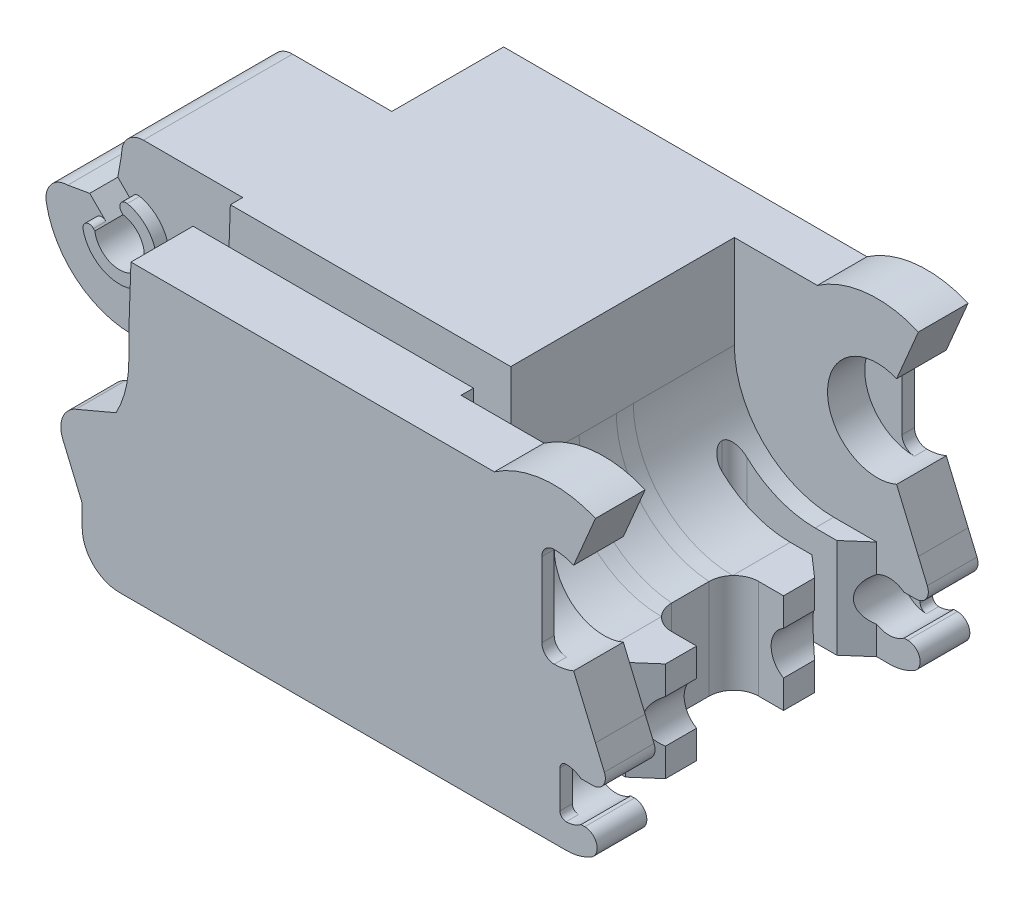
SolidWorks part; units mm, degrees
ref_plane "Front Plane" through (0, 0, 0) normal (0, 0, 1) x (1, 0, 0)
ref_plane "Top Plane" through (0, 0, 0) normal (0, 1, 0) x (1, 0, 0)
ref_plane "Right Plane" through (0, 0, 0) normal (1, 0, 0) x (0, 0, -1)
sketch "Sketch1" plane through (0, 0, 0) normal (0, 0, 1) x (1, 0, 0)
  line L0 (0, 0) -> (8.5, 0) construction
  line L1 (-52.5, 8.5) -> (8.5, 8.5)
  line L2 (-52.5, 8.5) -> (-52.5, -16.5)
  line L3 (-52.5, -16.5) -> (8.5, -16.5)
  line L4 (8.5, 8.5) -> (8.5, -16.5)
  line L5 (0, 0) -> (3.3212, 7.8243) construction
  line L6 (3.3212, 7.8243) -> (1.5629, 3.682)
  line L7 (3.3212, -7.8243) -> (1.5629, -3.682)
  line L8 (2.1605, -10.9) -> (2.1605, -14.1)
  line L9 (2.1605, -10.9) -> (4.6266, -10.9)
  line L10 (2.1605, -14.1) -> (4.6266, -14.1)
  line L11 (-42.7172, 1.9799) -> (-44.9799, -0.2828)
  line L12 (-52.5, -16.5) -> (-34, -16.5)
  line L13 (-52.5, -16.5) -> (-52.5, -6.5)
  line L16 (-42.7172, 1.9799) -> (-44.1314, 3.3941)
  line L17 (-48.1668, 0.8188) -> (-49.6208, 2.2728)
  line L18 (-43, 0) -> (-43.8485, 0.8485) construction
  line L19 (-46.3941, 1.1314) -> (-48.1668, 0.8188)
  line L20 (-43, 7) -> (-4.8218, 7)
  line L21 (-44.9799, -0.2828) -> (-46.3941, 1.1314)
  line L22 (-44.1314, 3.3941) -> (-43.8188, 5.1668)
  line L23 (-43.8188, 5.1668) -> (-45.2728, 6.6208)
  line L24 (-43, -7) -> (-34, -7)
  line L25 (-34, -7) -> (-34, -16.5)
  line L26 (4.6266, -10.9) -> (3.3212, -7.8243)
  line L27 (-34, -7) -> (-34, 0) construction
  line L28 (-38, -7) -> (-38, -16.5)
  line L29 (-43, 0) -> (-45, 0) construction
  circle A0 centre (0, 0) radius 2 construction
  circle A1 centre (-43, 0) radius 2
  circle A2 centre (0, 0) radius 4
  circle A3 centre (0, 0) radius 8.5
  circle A4 centre (0.9605, -12.5) radius 2
  circle A5 centre (0.9605, -12.5) radius 4
  circle A6 centre (-43, 0) radius 7
  circle A8 centre (-43, 0) radius 8.5 construction
  circle A9 centre (-43, 0) radius 9 construction
  point P39 (4.9605, -12.5)
  dimension "D1" = 4
  dimension "D2" = 4
  dimension "D4" = 8
  dimension "D9" = 4
  dimension "D13" = 8
  dimension "D20" = 17
  dimension "D23" = 17
  dimension "D3" = 43
  dimension "D5" = 25
  dimension "D6" = 9.5
  dimension "D8" = 67
  dimension "D10" = 2
  dimension "D12" = 3.2
  dimension "D16" = 3.2
  dimension "D14" = 2
  dimension "D15" = 4.9605
  dimension "D24" = 9
  dimension "D21" = 5
  dimension "D18" = 125
  dimension "D19" = 1.8
  dimension "D25" = 45
  dimension "D7" = 4.5
  dimension "D11" = 2
  dimension "D17" = 5
  dimension "D22" = 0.5
extrude "Boss-Extrude1" add sketch "Sketch1" along normal mid plane 30 contours A6 L23 L22 L16 A1 L21 L19 L17 | L6 A3 L7 A2 | A6 L24 L25 L3 A5 L26 A3 L20 | L9 A5 L10 A4 region at (1.6533, 8.1265, 0) region at (-20.6114, -4.9136, 0) region at (-38.1903, 4.8097, 0) region at (3.3935, -10.7892, 0)
fillet "Fillet1" radius 1 2 edges at (4.6266, -14.1, 0) (4.6266, -10.9, 0)
sketch "Sketch3" plane through (0, 0, 0) normal (0, 0, 1) x (1, 0, 0)
  line L0 (-34, -16.5) -> (0.9605, -16.5) construction
  line L1 (-11.5, 10.2107) -> (7.5521, 10.2107)
  line L2 (-11.5, 10.2107) -> (-11.5, -16.5)
  line L3 (-11.5, -16.5) -> (7.5521, -16.5)
  line L4 (7.5521, 10.2107) -> (7.5521, -16.5)
  dimension "D1" = 11.5
extrude "Cut-Extrude1" cut sketch "Sketch3" against normal offset from surface 4 and the other way offset from surface 4 contours L4 L1 L2 L3 region at (-1.9739, -3.1446, 0) up to face at (-21.008, -3.7662, -15) other way up to face at (-21.008, -3.7662, 15)
sketch "Sketch5" plane through (0, 0, 15) normal (0, 0, 1) x (1, 0, 0)
  line L0 (-43, 7) -> (-4.8218, 7) construction
  line L1 (-34, -7) -> (-73.6432, -7)
  line L2 (-34, -7) -> (-34, 7)
  line L3 (-34, 7) -> (-73.6432, 7)
  line L4 (-73.6432, -7) -> (-73.6432, 7)
extrude "Cut-Extrude2" cut sketch "Sketch5" against normal offset from surface (9 mm away) 5 up to face at (-0.5679, -6.687, 11) offset beyond the face yes
sketch "Sketch6" plane through (0, 0, -15) normal (0, 0, -1) x (-1, 0, 0)
  line L8 (34, -7) -> (73.6432, -7)
  line L9 (73.6432, -7) -> (73.6432, 7)
  line L10 (73.6432, 7) -> (34, 7)
  line L11 (34, 7) -> (34, -7)
  line L12 (34, -7) -> (73.6432, -7)
  line L13 (73.6432, -7) -> (73.6432, 7)
  line L14 (73.6432, 7) -> (34, 7)
  line L15 (34, 7) -> (34, -7)
  line M10 (34, -7) -> (43, -7)
  arc M11 (43, -7) -> (49.6208, 2.2728) centre (43, 0) ccw
  line M12 (49.6208, 2.2728) -> (48.1668, 0.8188)
  line M13 (48.1668, 0.8188) -> (46.3941, 1.1314)
  line M14 (46.3941, 1.1314) -> (44.9799, -0.2828)
  arc M15 (44.9799, -0.2828) -> (42.7172, 1.9799) centre (43, 0) cw
  line M16 (42.7172, 1.9799) -> (44.1314, 3.3941)
  line M17 (44.1314, 3.3941) -> (43.8188, 5.1668)
  line M18 (43.8188, 5.1668) -> (45.2728, 6.6208)
  arc M19 (45.2728, 6.6208) -> (43, 7) centre (43, 0) ccw
  line M20 (43, 7) -> (4.8218, 7)
  dimension "D1" = 0
extrude "Cut-Extrude3" cut sketch "Sketch6" against normal offset from surface (9 mm away) 5 contours M10 M11 M12 M13 M14 M15 M16 M17 M18 M19 M20 region at (-40.4606, -0.4936, -15) up to face at (-0.5679, -6.687, -11) offset beyond the face yes
sketch "Sketch7" plane through (0, 0, 0) normal (0, 0, 1) x (1, 0, 0)
  line L9 (-45.2728, 6.6208) -> (-43.8188, 5.1668)
  line L10 (-45.2728, 6.6208) -> (-43.8188, 5.1668)
  line L11 (-43.8188, 5.1668) -> (-44.1314, 3.3941)
  line L12 (-43.8188, 5.1668) -> (-44.1314, 3.3941)
  line L13 (-44.1314, 3.3941) -> (-42.7172, 1.9799)
  line L14 (-44.1314, 3.3941) -> (-42.7172, 1.9799)
  line L15 (-34, 7) -> (-43, 7)
  line L16 (-34, -7) -> (-34, 7)
  line L17 (-44.9799, -0.2828) -> (-46.3941, 1.1314)
  line L25 (-34, -7) -> (-34, 7)
  line L27 (-44.9799, -0.2828) -> (-46.3941, 1.1314)
  line L28 (-46.3941, 1.1314) -> (-48.1668, 0.8188)
  line L29 (-46.3941, 1.1314) -> (-48.1668, 0.8188)
  line L30 (-48.1668, 0.8188) -> (-49.6208, 2.2728)
  line L31 (-48.1668, 0.8188) -> (-49.6208, 2.2728)
  line L32 (-34, 7) -> (-43, 7)
  line L34 (-43, -7) -> (-34, -7)
  line L37 (-43, -7) -> (-34, -7)
  arc A1 (-43, 7) -> (-45.2728, 6.6208) centre (-43, 0) ccw
  arc A5 (-43, 7) -> (-45.2728, 6.6208) centre (-43, 0) ccw
  arc A9 (-44.9799, -0.2828) -> (-42.7172, 1.9799) centre (-43, 0) ccw
  arc A10 (-44.9799, -0.2828) -> (-42.7172, 1.9799) centre (-43, 0) ccw
  arc A11 (-49.6208, 2.2728) -> (-43, -7) centre (-43, 0) ccw
  arc A12 (-49.6208, 2.2728) -> (-43, -7) centre (-43, 0) ccw
  dimension "D1" = 0
fillet "Fillet2" radius 1.75 2 edges at (-49.6208, 2.2728, 0) (-45.2728, 6.6208, 0)
sketch "Sketch8" [suppressed] plane through (0, 0, -4.25) normal (0, 0, 1) x (1, 0, 0)
  line L0 (-53, 7) -> (-43, 7)
  line L1 (-43, 7) -> (-43, -7)
  line L2 (-43, -7) -> (-53, -7)
  arc A0 (-54.9799, -0.2828) -> (-52.7172, 1.9799) centre (-53, 0) ccw construction
  arc A1 (-54.9799, -0.2828) -> (-52.7172, 1.9799) centre (-53, 0) ccw
  circle A2 centre (-53, 0) radius 6 construction
  circle A3 centre (-53, 0) radius 7
  dimension "D1" = 17
sketch "Sketch10" plane through (0, 0, 6) normal (0, 0, 1) x (1, 0, 0)
  line L0 (-34.25, 0) -> (-34.25, 7)
  line L1 (-38, -7) -> (-38, -16.5) construction
  line L2 (-38, -7) -> (-38, -16.5)
  line L3 (-34, 7) -> (-37.75, 7)
  line L6 (-42.0708, 7) -> (-34, 7) construction
  line L7 (-34, 7) -> (-34, -16.5)
  line L8 (-34, -16.5) -> (-38, -16.5)
  arc A0 (3.3212, 7.8243) -> (-4.8218, 7) centre (0, 0) ccw construction
  arc A1 (-44.9799, -0.2828) -> (-42.7172, 1.9799) centre (-43, 0) ccw construction
  arc A2 (3.3212, 7.8243) -> (-4.8218, 7) centre (0, 0) ccw construction
  arc A3 (-44.9799, -0.2828) -> (-42.7172, 1.9799) centre (-43, 0) ccw construction
  circle A4 centre (-43, 0) radius 8.75
  line M9 (-43, -7) -> (-34, -7)
  line M10 (-34, -7) -> (-34, 7)
  line M11 (-34, 7) -> (-42.0708, 7)
  dimension "D1" = 8.5
  dimension "D2" = 17.5
extrude "Boss-Extrude3" add sketch "Sketch10" along normal up to surface (9 mm away) contours A4 M9 M10 M11 | A4 L2 L8 L7 M9 region at (-34.8884, -3.6133, 6) region at (-35.9988, -11.7528, 6) up to face at (-3.7821, -6.687, 15)
sketch "Sketch41" plane through (0, 0, -6) normal (0, 0, -1) x (-1, 0, 0)
  line L0 (34, 7) -> (37.75, 7) construction
  line L1 (34, 7) -> (34, -16.5) construction
  line L2 (34, -16.5) -> (38, -16.5) construction
  line L3 (38, -7) -> (38, -16.5) construction
  line L4 (34, 7) -> (37.75, 7)
  line L5 (34, 7) -> (34, -16.5)
  line L6 (34, -16.5) -> (38, -16.5)
  line L7 (38, -7) -> (38, -16.5)
  line L8 (34.25, 0) -> (34.25, 7)
  line L9 (34.25, 7) -> (34, 7)
  circle A1 centre (43, 0) radius 8.75
  circle A2 centre (43, 0) radius 8.75
  line M10 (42.0708, 7) -> (34, 7)
  line M11 (34, 7) -> (34, -7)
  line M12 (34, -7) -> (43, -7)
  dimension "D1" = 0
extrude "Boss-Extrude6" add sketch "Sketch41" along normal up to surface (9 mm away) contours A2 L5 L6 L7 M12 | A2 M10 M11 M12 region at (-34.8884, -3.6133, -6) region at (-35.9988, -11.7528, -6) up to face at (-3.7821, -6.687, -15)
sketch "Sketch66" plane through (0, 0, 15) normal (0, 0, 1) x (1, 0, 0)
  line L0 (-38, -11.7807) -> (-40.3444, -6.2577)
  line L1 (-38, -7.1807) -> (-38, -16.5) construction
  line L2 (-40.3444, -6.2577) -> (-35.2726, -4.1048)
  line L3 (-38, -7.1807) -> (-38, -16.5)
  arc A0 (-37.75, -7) -> (-34.25, 0) centre (-43, 0) ccw construction
  arc A1 (-38, -7.1807) -> (-34.25, 0) centre (-43, 0) ccw construction
  arc A2 (-38, -7.1807) -> (-34.25, 0) centre (-43, 0) ccw
  arc M4 (-34.25, 0) -> (-38, -7.1807) centre (-43, 0) cw
  line M5 (-38, -7.1807) -> (-38, -16.5)
  dimension "D1" = 23
  dimension "D2" = 4.6
  dimension "D3" = 6
extrude "Boss-Extrude11" add sketch "Sketch66" against normal blind 4 contours L2 L0 M5 M4 region at (-38.2402, -7.1014, 15)
sketch "Sketch74" plane through (0, 0, -15) normal (0, 0, -1) x (-1, 0, 0)
  line L0 (38, -11.7807) -> (38, -7.1807)
  line L10 (40.3444, -6.2577) -> (35.2726, -4.1048)
  line L11 (38, -11.7807) -> (40.3444, -6.2577)
  line L12 (38, -16.5) -> (38, -11.7807)
  line L13 (-0.9605, -16.5) -> (38, -16.5)
  line L14 (-2.1605, -14.1) -> (-2.4572, -14.1)
  line L15 (-3.1158, -10.9) -> (-2.1605, -10.9)
  line L16 (-3.3212, -7.8243) -> (-4.0363, -9.5093)
  line L17 (-1.5629, -3.682) -> (-3.3212, -7.8243)
  line L18 (-3.3212, 7.8243) -> (-1.5629, 3.682)
  line L19 (34.25, 7) -> (4.8218, 7)
  line L20 (40.3444, -6.2577) -> (35.2726, -4.1048)
  line L21 (38, -11.7807) -> (40.3444, -6.2577)
  line L22 (38, -16.5) -> (38, -11.7807)
  line L23 (-0.9605, -16.5) -> (38, -16.5)
  line L24 (-2.1605, -14.1) -> (-2.4572, -14.1)
  line L25 (-3.1158, -10.9) -> (-2.1605, -10.9)
  line L26 (-3.3212, -7.8243) -> (-4.0363, -9.5093)
  line L27 (-1.5629, -3.682) -> (-3.3212, -7.8243)
  line L28 (-3.3212, 7.8243) -> (-1.5629, 3.682)
  line L29 (34.25, 7) -> (4.8218, 7)
  line L32 (34.25, 0) -> (34.25, 7)
  line L33 (34.25, 0) -> (34.25, 7)
  arc A0 (35.2726, -4.1048) -> (38, -7.1807) centre (43, 0) ccw
  arc A7 (34.25, 0) -> (35.2726, -4.1048) centre (43, 0) ccw
  arc A8 (-2.956, -15.9667) -> (-0.9605, -16.5) centre (-0.9605, -12.5) ccw
  arc A9 (-2.4572, -14.1) -> (-2.956, -15.9667) centre (-2.4572, -15.1) ccw
  arc A10 (-2.1605, -14.1) -> (-2.1605, -10.9) centre (-0.9605, -12.5) ccw
  arc A11 (-4.0363, -9.5093) -> (-3.1158, -10.9) centre (-3.1158, -9.9) ccw
  arc A12 (-1.5629, -3.682) -> (-1.5629, 3.682) centre (0, 0) ccw
  arc A13 (4.8218, 7) -> (-3.3212, 7.8243) centre (0, 0) ccw
  arc A14 (34.25, 0) -> (35.2726, -4.1048) centre (43, 0) ccw
  arc A15 (-2.956, -15.9667) -> (-0.9605, -16.5) centre (-0.9605, -12.5) ccw
  arc A16 (-2.4572, -14.1) -> (-2.956, -15.9667) centre (-2.4572, -15.1) ccw
  arc A17 (-2.1605, -14.1) -> (-2.1605, -10.9) centre (-0.9605, -12.5) ccw
  arc A18 (-4.0363, -9.5093) -> (-3.1158, -10.9) centre (-3.1158, -9.9) ccw
  arc A19 (-1.5629, -3.682) -> (-1.5629, 3.682) centre (0, 0) ccw
  arc A20 (4.8218, 7) -> (-3.3212, 7.8243) centre (0, 0) ccw
  line M19 (38, -16.5) -> (38, -7.1807)
  arc M20 (38, -7.1807) -> (34.25, 0) centre (43, 0) cw
  dimension "D1" = 0
extrude "Boss-Extrude12" add sketch "Sketch74" against normal blind 4 contours L21 L20 M19 M20 region at (-38.2402, -7.1014, -15)
fillet "Fillet4" radius 2 2 edges at (-40.3444, -6.2577, 13) (-40.3444, -6.2577, -13)
ref_plane "Plane1" through (0, 0, 8.5) normal (0, 0, 1) x (1, 0, 0)
sketch "Sketch11" plane through (0, 0, 8.5) normal (0, 0, -1) x (-1, 0, 0)
  line L0 (41.593, 5.317) -> (1.407, -5.317)
  arc A0 (42.7172, 1.9799) -> (44.9799, -0.2828) centre (43, 0) ccw construction
  arc A1 (42.7172, 1.9799) -> (44.9799, -0.2828) centre (43, 0) ccw construction
  arc A2 (-1.5629, -3.682) -> (-1.5629, 3.682) centre (0, 0) ccw construction
  arc A3 (-1.5629, -3.682) -> (-1.5629, 3.682) centre (0, 0) ccw construction
  circle A4 centre (43, 0) radius 5 construction
  circle A5 centre (0, 0) radius 5 construction
  circle A6 centre (43, 0) radius 5.5 construction
  circle A7 centre (0, 0) radius 5.5 construction
  dimension "D1" = 10
  dimension "D3" = 0.5
sweep "Cut-Sweep1" cut path "Sketch11" circular profile diameter 3 parameters "D3"=3
fillet "Fillet6" radius 3 2 edges at (-38, -16.5, 10.5) (-38, -16.5, -10.5)
sketch "Sketch24" plane through (0, 0, 0) normal (0, 0, 1) x (1, 0, 0)
  line L0 (-35, -16.5) -> (0.9605, -16.5) construction
  line L1 (-35, -16.5) -> (0.9605, -16.5) construction
  line L6 (-25.5, -14.5) -> (-25.5, -16.5) construction
  line L7 (-10.5, -14.5) -> (-10.5, -16.5) construction
  line L8 (-35.5, -14.5) -> (-35.5, -16.5)
  line L9 (-20.5, -14.5) -> (-20.5, -16.5)
  line L10 (-35.5, -16.5) -> (-20.5, -16.5)
  line L11 (-25.5, -16.5) -> (-10.5, -16.5) construction
  line L12 (-28, -7) -> (-38, -7)
  line L13 (-38, -11.7807) -> (-38, -13.5) construction
  line L14 (-38, -7) -> (-38, -16.5)
  line L15 (-38, -16.5) -> (-20.5, -16.5)
  circle A0 centre (-18, -14.5) radius 2 construction
  arc A5 (-44.9799, -0.2828) -> (-42.7172, 1.9799) centre (-43, 0) ccw construction
  arc A6 (-44.9799, -0.2828) -> (-42.7172, 1.9799) centre (-43, 0) ccw construction
  circle A7 centre (-28, -14.5) radius 2 construction
  arc A8 (-10.5, -14.5) -> (-25.5, -14.5) centre (-18, -14.5) ccw construction
  arc A9 (-20.5, -14.5) -> (-35.5, -14.5) centre (-28, -14.5) ccw
  circle A10 centre (-18, -14.5) radius 2.2 construction
  circle A11 centre (-28, -14.5) radius 2.2
  dimension "D1" = 4
  dimension "D2" = 18
  dimension "D3" = 5.5
  dimension "D4" = 15
  dimension "D5" = 0.2
extrude "Cut-Extrude6" cut sketch "Sketch24" against normal up to surface and the other way up to surface contours A10 L11 L7 A8 L6 | A11 L10 L9 A9 L8 | A9 L12 L14 L15 L8 region at (-28, -12.075, 0) region at (-35.7642, -10.7139, 0) up to face at (-36.2284, -11.3839, -6) other way up to face at (-36.2284, -11.3839, 6)
sketch "Sketch45" plane through (0, 0, 0) normal (0, 0, 1) x (1, 0, 0)
  line L0 (3.3212, -7.8243) -> (1.5629, -3.682) construction
  line L1 (3.3212, -7.8243) -> (1.5629, -3.682)
  arc A0 (2.1605, -10.9) -> (2.1605, -14.1) centre (0.9605, -12.5) ccw construction
  arc A1 (2.1605, -10.9) -> (2.1605, -14.1) centre (0.9605, -12.5) ccw
sketch "Sketch47" plane through (0, 7, 0) normal (0, 1, 0) x (1, 0, 0)
  line L0 (-11.5, -7) -> (-34.25, -7) construction
  line L1 (-5.5113, -7) -> (-48.8713, -7)
  line L2 (-34.25, -10) -> (-11.5, -10) construction
  line L3 (-48.8713, -10) -> (-5.5113, -10)
  line L4 (-48.8713, -10) -> (-48.8713, -7)
  line L5 (-5.5113, -7) -> (-5.5113, -10)
extrude "Cut-Extrude7" cut sketch "Sketch47" against normal up to surface (11.2309 mm away) up to face at (-34.25, 1.8223, 8.5)
sketch "Sketch50" plane through (0, 0, 11) normal (0, 0, -1) x (-1, 0, 0)
  line L0 (0.0395, -14.2321) -> (0.0395, -16.5)
  line L1 (11.5, -16.5) -> (-0.9605, -16.5) construction
  line L2 (11.5, 7) -> (11.5, -16.5) construction
  line L3 (11.5, 7) -> (11.5, -16.5)
  line L4 (0.0395, -16.5) -> (11.5, -16.5)
  line L5 (0.0395, -10.7679) -> (0.0395, -8.5)
  line L6 (0.0395, -8.5) -> (11.5, -8.5)
  arc A0 (-2.1605, -14.1) -> (-2.1605, -10.9) centre (-0.9605, -12.5) ccw construction
  arc A1 (-2.1605, -14.1) -> (-2.1605, -10.9) centre (-0.9605, -12.5) ccw
  arc M11 (-2.1605, -10.9) -> (-2.1605, -14.1) centre (-0.9605, -12.5) cw
  line M15 (-0.9605, -16.5) -> (11.5, -16.5)
  line M16 (11.5, -16.5) -> (11.5, 7)
  dimension "D1" = 4
  dimension "D2" = 4
extrude "Boss-Extrude7" add sketch "Sketch50" along normal up to vertex contours L6 L5 L0 M11 M15 M16 region at (-5.9162, -12.5, 11) up to point (0.9605, -16.5, -11)
sketch "Sketch51" plane through (0, -16.5, 0) normal (0, -1, 0) x (1, 0, 0)
  line L0 (-0.0395, -11) -> (-0.0395, 11) construction
  line L1 (-0.0395, -11) -> (-0.0395, 11)
  line L2 (-2.0395, 7.75) -> (-2.0395, 9.25)
  line L3 (-2.0395, 9.25) -> (-0.0395, 11)
  line L4 (-2.0395, 8.5) -> (-0.0395, 8.5) construction
  line L5 (-2.0395, 7.75) -> (-0.0395, 6)
  line L6 (-0.0395, 0) -> (-3.9441, 0) construction
  line L7 (-2.0395, -7.75) -> (-0.0395, -6)
  line L8 (-2.0395, -7.75) -> (-2.0395, -9.25)
  line L9 (-2.0395, -9.25) -> (-0.0395, -11)
  line L12 (-0.0395, 3.5) -> (-0.0395, -4)
  line L13 (-0.0395, 3.5) -> (-4.0395, 3.5)
  line L14 (-0.0395, 3.5) -> (-0.0395, -3.5)
  line L15 (-0.0395, -3.5) -> (-4.0395, -3.5)
  line L16 (-4.0395, 3.5) -> (-4.0395, -3.5)
  point P1 (0, 0)
  point P2 (-2.0395, 8.5)
  point P6 (-2.0395, 8.5)
  point P17 (-4.0395, 0)
  point P20 (0, 0)
  point P21 (-0.0395, 11)
  line M26 (-0.0395, -11) -> (-0.0395, 11)
  dimension "D1" = 2.5
  dimension "D2" = 1.5
  dimension "D4" = 7
  dimension "D5" = 4
extrude "Cut-Extrude8" cut sketch "Sketch51" against normal up to surface (8 mm away) contours L2 L5 L1 L3 | L8 L9 L7 M26 | L13 L16 L15 L12 region at (-0.86, -16.5, -8.5) region at (-0.86, -16.5, 8.5) region at (-2.0395, -16.5, 0) up to face at (-5.7698, -8.5, 0)
fillet "Fillet10" radius 2 2 edges at (-4.0395, -12.5, 3.5) (-4.0395, -12.5, -3.5)
fillet "Fillet11" radius 8 1 edges at (-11.5, -8.5, 0)
sketch "Sketch52" plane through (0, 0, -6) normal (0, 0, -1) x (-1, 0, 0)
  line L0 (46.3941, 1.1314) -> (44.9799, -0.2828) construction
  line L1 (42.7172, 1.9799) -> (44.1314, 3.3941) construction
  line L2 (45.9258, 0.6631) -> (44.9799, -0.2828)
  line L3 (42.7172, 1.9799) -> (43.6631, 2.9258)
  arc A0 (42.7172, 1.9799) -> (44.9799, -0.2828) centre (43, 0) ccw construction
  arc A1 (42.7172, 1.9799) -> (44.9799, -0.2828) centre (43, 0) ccw
  circle A2 centre (43, 0) radius 3
  line M9 (46.3941, 1.1314) -> (44.9799, -0.2828)
  arc M10 (44.9799, -0.2828) -> (42.7172, 1.9799) centre (43, 0) cw
  line M11 (42.7172, 1.9799) -> (44.1314, 3.3941)
  dimension "D1" = 6
extrude "Boss-Extrude8" add sketch "Sketch52" along normal blind 1 contours A2 M11 M9 M10 region at (-45.8971, 0.3242, -6)
fillet "Fillet13" radius 0.5 2 edges at (-45.9258, 0.6631, -6.5) (-43.6631, 2.9258, -6.5)
mirror "Mirror1" about plane through (0, 0, 0) normal (0, 0, 1) of "Fillet13", "Boss-Extrude8"
sketch "Sketch62" plane through (0, 0, 15) normal (0, 0, 1) x (1, 0, 0)
  line L0 (-1, 3.873) -> (-1, -3.873)
  circle A0 centre (0, 0) radius 2 construction
  arc A1 (1.5629, 3.682) -> (1.5629, -3.682) centre (0, 0) ccw construction
  arc A2 (-1, 3.873) -> (-1, -3.873) centre (0, 0) ccw
  dimension "D1" = 4
  dimension "D2" = 1
  dimension "D3" = 1
extrude "Boss-Extrude9" add sketch "Sketch62" against normal blind 1
fillet "Fillet14" radius 1 2 edges at (-1, -3.873, 14.5) (-1, 3.873, 14.5)
mirror "Mirror2" about plane through (0, 0, 0) normal (0, 0, 1) of "Fillet14", "Boss-Extrude9"
sketch "Sketch63" plane through (0, 0, -15) normal (0, 0, -1) x (-1, 0, 0)
  line L0 (-0.4605, -10.5635) -> (-0.4605, -14.4365)
  arc A0 (-2.1605, -14.1) -> (-2.1605, -10.9) centre (-0.9605, -12.5) ccw construction
  arc A1 (-0.4605, -10.5635) -> (-0.4605, -14.4365) centre (-0.9605, -12.5) cw
  dimension "D1" = 1.5
extrude "Boss-Extrude10" add sketch "Sketch63" against normal blind 1
fillet "Fillet15" radius 0.5 2 edges at (0.4605, -10.5635, -14.5) (0.4605, -14.4365, -14.5)
mirror "Mirror3" about plane through (0, 0, 0) normal (0, 0, 1) of "Fillet15", "Boss-Extrude10"
chamfer "Chamfer1" distance 5 angle 2 2 edges at (-34.25, 7, 6.5) (-34.25, 7, 12.5) first distance on face at (-34.25, 4.1495, 9.5)
chamfer "Chamfer2" distance 5 angle 2 1 edges at (-34.25, 7, -10.5) first distance on face at (-34.25, 3.5, -10.5)
fillet "Fillet16" radius 2 2 edges at (-38, -7.1807, 8.5) (-38, -7.1807, -8.5)
sketch "Sketch80" plane through (0, -16.5, 0) normal (0, -1, 0) x (1, 0, 0)
  line L0 (-1.7538, -9.5) -> (-10, -9.5)
  line L1 (-10, -9.5) -> (-10, -7.5)
  line L2 (-10, -7.5) -> (-1.7538, -7.5)
  line L3 (0, 0) -> (-4.0395, 0) construction
  line L4 (-1.7538, -9.5) -> (-2.0395, -9.25)
  line L5 (-2.0395, -9.25) -> (-2.0395, -7.75)
  line L6 (-2.0395, -7.75) -> (-1.7538, -7.5)
  line L7 (-2.0395, 7.75) -> (-1.7538, 7.5)
  line L8 (-2.0395, 9.25) -> (-2.0395, 7.75)
  line L9 (-1.7538, 9.5) -> (-2.0395, 9.25)
  line L10 (-1.7538, 9.5) -> (-10, 9.5)
  line L11 (-10, 7.5) -> (-1.7538, 7.5)
  line L12 (-10, 9.5) -> (-10, 7.5)
  line L22 (-0.0395, 3.5) -> (-0.0395, 6)
  line L23 (-0.0395, 6) -> (-2.0395, 7.75)
  line L24 (-2.0395, 7.75) -> (-2.0395, 9.25)
  line L25 (-2.0395, 9.25) -> (-0.0395, 11)
  line L26 (-0.0395, 11) -> (0.9605, 11)
  line L27 (0.9605, 11) -> (0.9605, 15)
  line L28 (0.9605, 15) -> (-35, 15)
  line L29 (-35, 15) -> (-35, 6)
  line L30 (-35, 6) -> (-28.9165, 6)
  line L31 (-28.9165, 6) -> (-28.9165, -6)
  line L32 (-28.9165, -6) -> (-35, -6)
  line L33 (-35, -6) -> (-35, -15)
  line L34 (-35, -15) -> (0.9605, -15)
  line L35 (0.9605, -15) -> (0.9605, -11)
  line L36 (0.9605, -11) -> (-0.0395, -11)
  line L37 (-0.0395, -11) -> (-2.0395, -9.25)
  line L38 (-2.0395, -9.25) -> (-2.0395, -7.75)
  line L39 (-2.0395, -7.75) -> (-0.0395, -6)
  line L40 (-0.0395, -6) -> (-0.0395, -3.5)
  line L41 (-0.0395, -3.5) -> (-2.0395, -3.5)
  line L42 (-4.0395, -1.5) -> (-4.0395, 1.5)
  line L43 (-2.0395, 3.5) -> (-0.0395, 3.5)
  line L44 (-0.0395, 3.5) -> (-0.0395, 6) construction
  line L45 (-0.0395, 6) -> (-2.0395, 7.75) construction
  line L46 (-2.0395, 7.75) -> (-2.0395, 9.25) construction
  line L47 (-2.0395, 9.25) -> (-0.0395, 11) construction
  line L48 (-0.0395, 11) -> (0.9605, 11) construction
  line L49 (0.9605, 11) -> (0.9605, 15) construction
  line L50 (0.9605, 15) -> (-35, 15) construction
  line L51 (-35, 15) -> (-35, 6) construction
  line L52 (-35, 6) -> (-28.9165, 6) construction
  line L53 (-28.9165, 6) -> (-28.9165, -6) construction
  line L54 (-28.9165, -6) -> (-35, -6) construction
  line L55 (-35, -6) -> (-35, -15) construction
  line L56 (-35, -15) -> (0.9605, -15) construction
  line L57 (0.9605, -15) -> (0.9605, -11) construction
  line L58 (0.9605, -11) -> (-0.0395, -11) construction
  line L59 (-0.0395, -11) -> (-2.0395, -9.25) construction
  line L60 (-2.0395, -9.25) -> (-2.0395, -7.75) construction
  line L61 (-2.0395, -7.75) -> (-0.0395, -6) construction
  line L62 (-0.0395, -6) -> (-0.0395, -3.5) construction
  line L63 (-0.0395, -3.5) -> (-2.0395, -3.5) construction
  line L64 (-4.0395, -1.5) -> (-4.0395, 1.5) construction
  line L65 (-2.0395, 3.5) -> (-0.0395, 3.5) construction
  arc A2 (-4.0395, -1.5) -> (-2.0395, -3.5) centre (-2.0395, -1.5) ccw
  arc A3 (-2.0395, 3.5) -> (-4.0395, 1.5) centre (-2.0395, 1.5) ccw
  arc A4 (-4.0395, -1.5) -> (-2.0395, -3.5) centre (-2.0395, -1.5) ccw construction
  arc A5 (-2.0395, 3.5) -> (-4.0395, 1.5) centre (-2.0395, 1.5) ccw construction
  point P26 (-10, -8.5)
  point P28 (0, 0)
  point P30 (-2.0395, -8.5)
  dimension "D2" = 10
  dimension "D3" = 2
  dimension "D1" = 0
extrude "Cut-Extrude9" cut sketch "Sketch80" against normal blind 12
fillet "Fillet17" radius 1 4 edges at (-10, -10.8318, 7.5) (-10, -10.8318, 9.5) (-10, -10.8318, -7.5) (-10, -10.8318, -9.5)
equation "\"mainSnapAngle\"= 67deg"
equation "\"D8@Sketch1\"=\"mainSnapAngle\""
equation "\"jointDistance\"= 43mm"
equation "\"mountBearingOD\"= 8mm"
equation "\"D3@Sketch1\"=\"jointDistance\""
equation "\"D4@Sketch1\"=\"mountBearingOD\""
equation "\"shaftDiameter\"= 4mm"
equation "\"D12@Sketch1\"=\"shaftDiameter\"*0.8"
equation "\"D2@Sketch1\"=\"shaftDiameter\""
equation "\"D1@Sketch1\"=\"shaftDiameter\""
equation "\"D16@Sketch1\"=\"D2@Sketch1\"*0.8"
equation "\"UgrooveOD\"= 17mm"
equation "\"D20@Sketch1\"=\"UgrooveOD\""
equation "\"D1@Sketch8\"=\"UgrooveOD\""
equation "\"D24@Sketch1\"= \"D23@Sketch1\" / 2 + 0.5"
equation "\"D2@Sketch10\"=\"D1@Sketch10\"*2+0.5"
equation "\"grooveDiameter\"= 10mm"
equation "\"tendonDiameter\"= 1mm"
equation "\"D3@Sketch11\"=\"tendonDiameter\"/2"
equation "\"D1@Sketch11\"=\"grooveDiameter\""
equation "\"D1@Sketch3\"=\"UgrooveOD\"/2+3"
equation "\"D2@Sketch50\"=\"D1@Sketch50\""
equation "\"D2@Sketch51\"=\"tendonDiameter\" +0.5"
equation "\"D3@Sketch51\"=2"
